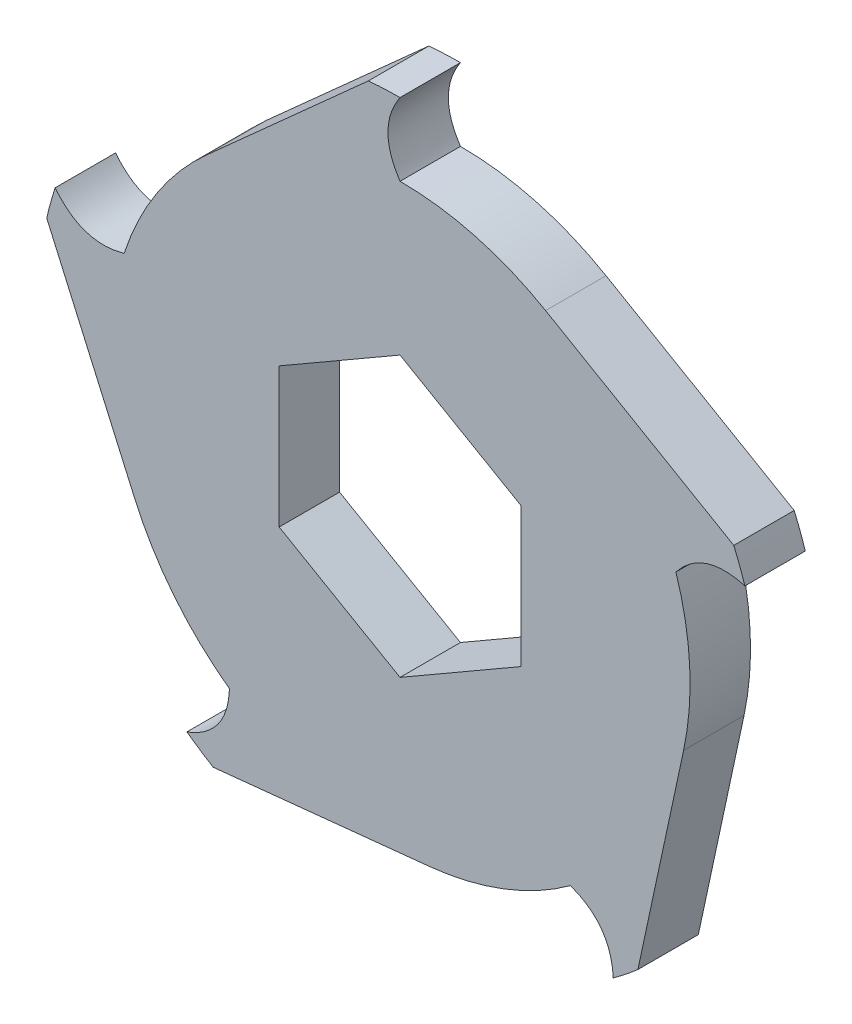
SolidWorks part; units mm, degrees
ref_plane "Front Plane" through (0, 0, 0) normal (0, 0, 1) x (1, 0, 0)
ref_plane "Top Plane" through (0, 0, 0) normal (0, 1, 0) x (1, 0, 0)
ref_plane "Right Plane" through (0, 0, 0) normal (1, 0, 0) x (0, 0, -1)
sketch "Sketch2" plane through (0, 0, 0) normal (0, 0, 1) x (1, 0, 0)
  line L0 (-3.3206, 37.955) -> (0, 0) construction
  line L1 (0, 30.48) -> (0, 38.1) construction
  line L2 (0, 0) -> (0, 38.1) construction
  line L3 (-3.3206, 37.955) -> (-20.3436, 22.6973)
  circle A0 centre (0, 0) radius 30.48
  arc A1 (0, 38.1) -> (-3.3206, 37.955) centre (0, 0) ccw
  arc A2 (0, 30.48) -> (-20.3436, 22.6973) centre (0, 0) ccw
  spline S0 degree 2 poles (0, 30.48) (-2.54, 34.29) (0, 38.1) knots 0 0 0 1 1 1
  point P9 (0, 34.29)
  point P32 (0, 0)
  dimension "D1" = 60.96
  dimension "D4" = 5
  dimension "D2" = 7.62
  dimension "D3" = 1.27
extrude "Boss-Extrude1" add sketch "Sketch2" along normal blind 6.35 contours A0 region at (0, 0, 0)
sketch "Sketch3" plane through (0, 0, 0) normal (0, 0, 1) x (1, 0, 0)
  line L0 (0, 0) -> (0, 14.6647) construction
  line L1 (0, 14.6647) -> (-12.7, 7.3323)
  line L2 (-12.7, 7.3323) -> (-12.7, -7.3323)
  line L3 (-12.7, -7.3323) -> (0, -14.6647)
  line L4 (0, -14.6647) -> (12.7, -7.3323)
  line L5 (12.7, -7.3323) -> (12.7, 7.3323)
  line L6 (12.7, 7.3323) -> (0, 14.6647)
  circle A0 centre (0, 0) radius 12.7 construction
  dimension "D1" = 25.4
extrude "Cut-Extrude1" cut sketch "Sketch3" against normal through all both and the other way through all
extrude "Boss-Extrude2" add sketch "Sketch2<3>" along normal blind 6.35 contours A0 S0 A1 L3 region at (-6.1509, 32.3465, 0)
sketch "Sketch2<3>" plane through (0, 0, 0) normal (0, 0, 1) x (1, 0, 0) same geometry as "Sketch2"
pattern_circular "CirPattern1" count 5 over 360 about axis through (0, 0, 6.35) along (0, 0, 1) of "Boss-Extrude2"
